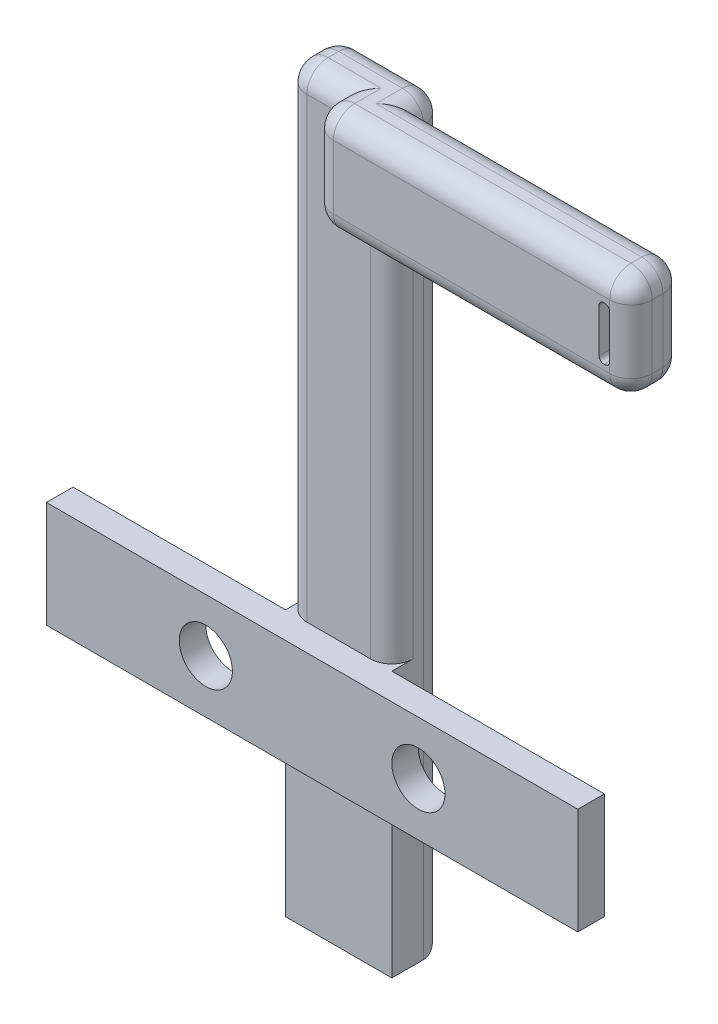
SolidWorks part; units mm, degrees
material "ABS PC"
ref_plane "Front Plane" through (0, 0, 0) normal (0, 0, 1) x (1, 0, 0)
ref_plane "Top Plane" through (0, 0, 0) normal (0, 1, 0) x (1, 0, 0)
ref_plane "Right Plane" through (0, 0, 0) normal (1, 0, 0) x (0, 0, -1)
sketch "Sketch1" plane through (0, 0, 0) normal (0, 0, 1) x (1, 0, 0)
  line L1 (-25, 5) -> (25, 5)
  line L2 (-25, 5) -> (-25, -5)
  line L3 (-25, -5) -> (25, -5)
  line L4 (25, 5) -> (25, -5)
  line L5 (-25, 5) -> (25, -5) construction
  line L6 (-25, -5) -> (25, 5) construction
  circle A0 centre (-10, 0) radius 2.5
  circle A1 centre (10, 0) radius 2.5
  point P0 (0, 0)
extrude "Boss-Extrude1" add sketch "Sketch1" along normal blind 2.5
sketch "Sketch2" plane through (0, 0, 0) normal (1, 0, 0) x (0, 0, -1)
  line L0 (0, 0) -> (0, 45)
  line L1 (0, 45) -> (2.5, 45)
ref_plane "Plane1" through (0, 0, -2.5) normal (0, 0, 1) x (1, 0, 0)
sketch "Sketch3" plane through (0, 0, -2.5) normal (0, 0, 1) x (1, 0, 0)
  line L0 (0, 45) -> (45, 45) construction
sketch "Sketch4" plane through (0, 0, 0) normal (1, 0, 0) x (0, 0, -1)
  line L0 (2.5, 40) -> (2.5, 50)
  line L1 (-2.5, 40) -> (2.5, 40)
  line L2 (-2.5, 40) -> (-2.5, 50)
  line L3 (-2.5, 50) -> (2.5, 50)
  line L5 (-2.5, 40) -> (2.5, 45) construction
  line L6 (-2.5, 50) -> (2.5, 45) construction
  point P0 (2.5, 45)
extrude "Boss-Extrude2" add sketch "Sketch4" along normal blind 30 separate body
sketch "Sketch5" plane through (0, 0, 0) normal (0, 1, 0) x (1, 0, 0)
  line L0 (0, 0) -> (0, 2.5) construction
  line L1 (-5, 5) -> (5, 5)
  line L2 (-5, 5) -> (-5, 0)
  line L3 (-5, 0) -> (5, 0)
  line L4 (5, 5) -> (5, 0)
  line L5 (-5, 5) -> (5, 0) construction
  line L6 (-5, 0) -> (5, 5) construction
  line L7 (0, 2.5) -> (45, 2.5) construction
  point P0 (0, 2.5)
extrude "Boss-Extrude3" add sketch "Sketch5" along normal blind 50 and the other way blind 20
fillet "Fillet4" radius 2 3 edges at (0, -20, -5) (5, 15, -5) (-5, 15, -5)
fillet "Fillet5" radius 2 1 edges at (5, 22.5, 0)
fillet "Fillet6" radius 2 10 edges at (15, 40, 2.5) (30, 40, 0) (30, 45, 2.5) (17.5, 40, -2.5) (17.5, 50, -2.5) (30, 45, -2.5) (30, 50, 0) (15, 50, 2.5) (0, 45, 2.5) (-5, 27.5, 0)
fillet "Fillet7" radius 2 7 edges at (5, 50, -1.75) (4.4142, 50, -4.4142) (0, 50, -5) (-4.4142, 50, -4.4142) (-5, 50, -2.5) (-4.4142, 50, -0.5858) (-1.5, 50, 0)
fillet "Fillet8" radius 2 4 edges at (0, 40, 0.25) (0, 50, -0.75) (0.5858, 40.5858, 1.9142) (0.5858, 49.4142, 1.9142)
sketch "Sketch7" plane through (0, 0, -2.5) normal (0, 0, -1) x (-1, 0, 0)
  line L0 (-30, 42) -> (-30, 48) construction
  line L1 (-27.55, 42.5) -> (-27.45, 42.5)
  line L2 (-28, 42.95) -> (-28, 47.05)
  line L3 (-27.55, 47.5) -> (-27.45, 47.5)
  line L4 (-27, 42.95) -> (-27, 47.05)
  line L5 (-28, 42.5) -> (-27, 47.5) construction
  line L6 (-28, 47.5) -> (-27, 42.5) construction
  arc A0 (-27, 47.05) -> (-27.45, 47.5) centre (-27.45, 47.05) ccw
  arc A1 (-28, 47.05) -> (-27.55, 47.5) centre (-27.55, 47.05) cw
  arc A2 (-27.55, 42.5) -> (-28, 42.95) centre (-27.55, 42.95) cw
  arc A3 (-27.45, 42.5) -> (-27, 42.95) centre (-27.45, 42.95) ccw
  point P0 (-27.5, 45)
  dimension "D1" = 0.45
  dimension "D2" = 2.5
extrude "Cut-Extrude2" cut sketch "Sketch7" against normal blind 10
